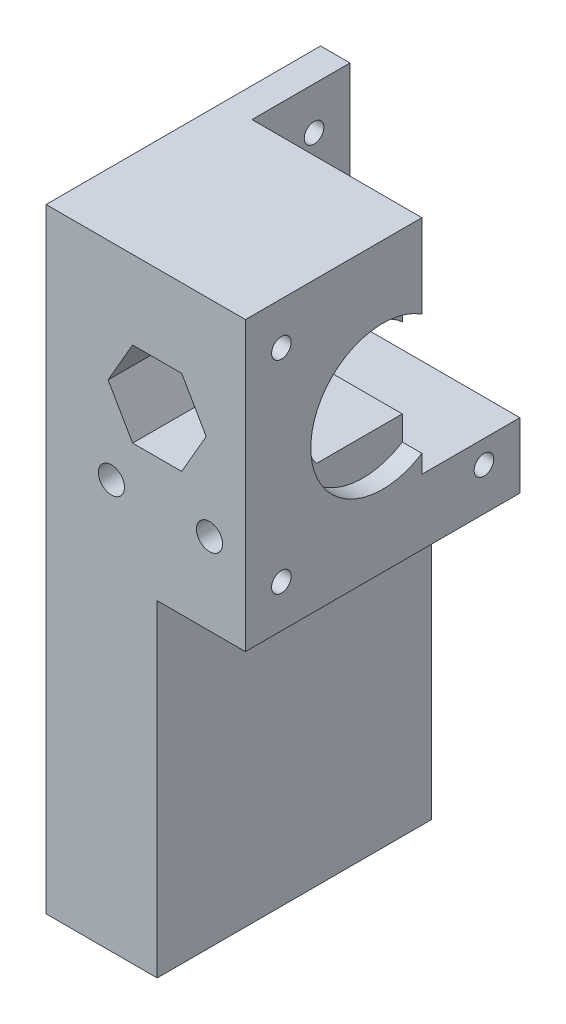
SolidWorks part; units mm, degrees
ref_plane "Front Plane" through (0, 0, 0) normal (0, 0, 1) x (1, 0, 0)
ref_plane "Top Plane" through (0, 0, 0) normal (0, 1, 0) x (1, 0, 0)
ref_plane "Right Plane" through (0, 0, 0) normal (1, 0, 0) x (0, 0, -1)
sketch "Sketch1" plane through (0, 0, 0) normal (0, 0, 1) x (1, 0, 0)
  line L1 (0, 0) -> (30.5, 0)
  line L2 (0, 0) -> (0, 44)
  line L3 (0, 44) -> (30.5, 44)
  line L4 (30.5, 0) -> (30.5, 44)
  line L5 (0, 0) -> (17, 0)
  line L6 (0, 0) -> (0, -50)
  line L7 (0, -50) -> (17, -50)
  line L8 (17, 0) -> (17, -50)
  dimension "D1" = 30.5
  dimension "D2" = 44
  dimension "D3" = 50
  dimension "D4" = 17
extrude "Boss-Extrude1" add sketch "Sketch1" along normal blind 42 contours L1 L4 L3 L2 | L8 L1 L6 L7 region at (15.25, 22, 0) region at (8.5, -25, 0)
sketch "Sketch2" plane through (30.5, 0, 0) normal (1, 0, 0) x (0, 0, -1)
  line L0 (-21, 44) -> (-21, 0) construction
  line L1 (-42, 44) -> (0, 44) construction
  line L2 (-42, 0) -> (0, 0) construction
  line L3 (-42, 22) -> (0, 22) construction
  line L4 (-42, 0) -> (-42, 44) construction
  line L5 (0, 0) -> (0, 44) construction
  circle A0 centre (-21, 22) radius 11
  circle A1 centre (-5.5, 37.5) radius 1.5
  circle A2 centre (-36.5, 37.5) radius 1.5
  circle A3 centre (-36.5, 6.5) radius 1.5
  circle A4 centre (-5.5, 6.5) radius 1.5
  circle A5 centre (-21, 22) radius 9
  point P15 (-21, 22)
  dimension "D1" = 22
  dimension "D2" = 3
  dimension "D3" = 31
  dimension "D4" = 31
  dimension "D5" = 18
extrude "Cut-Extrude1" cut sketch "Sketch2" against normal through all contours A5 | A4 | A3 | A1 | A2
sketch "Sketch4" plane through (30.5, 0, 0) normal (1, 0, 0) x (0, 0, -1)
  line L1 (0, 44) -> (-15, 44)
  line L2 (0, 44) -> (0, 10)
  line L3 (0, 10) -> (-15, 10)
  line L4 (-15, 44) -> (-15, 10)
  dimension "D1" = 15
  dimension "D2" = 34
extrude "Cut-Extrude4" cut sketch "Sketch4" against normal blind 26
sketch "Sketch5" plane through (0, 0, 15) normal (0, 0, -1) x (-1, 0, 0)
  line L1 (-4.5, 10) -> (-27.5, 10)
  line L2 (-4.5, 10) -> (-4.5, 16.5)
  line L3 (-4.5, 16.5) -> (-27.5, 16.5)
  line L4 (-27.5, 10) -> (-27.5, 16.5)
  dimension "D1" = 6.5
  dimension "D2" = 23
extrude "Boss-Extrude2" add sketch "Sketch5" against normal blind 20
sketch "Sketch3" plane through (0, 0, 42) normal (0, 0, 1) x (1, 0, 0)
  line L0 (0, 44) -> (30.5, 44) construction
  line L1 (13.2417, 19) -> (20.7472, 19)
  line L2 (20.7472, 19) -> (24.5, 25.5)
  line L3 (24.5, 25.5) -> (20.7472, 32)
  line L4 (20.7472, 32) -> (13.2417, 32)
  line L5 (13.2417, 32) -> (9.4889, 25.5)
  line L6 (9.4889, 25.5) -> (13.2417, 19)
  line L7 (30.5, 0) -> (30.5, 44) construction
  line L8 (17, 0) -> (30.5, 0) construction
  circle A0 centre (16.9944, 25.5) radius 6.5 construction
  circle A1 centre (25, 12.5) radius 2
  circle A2 centre (10, 12.5) radius 2
  circle A3 centre (25, 12.5) radius 2.5
  circle A4 centre (10, 12.5) radius 2.5
  dimension "D1" = 13
  dimension "D4" = 5.5
  dimension "D5" = 15
  dimension "D6" = 4
  dimension "D7" = 5
  dimension "D8" = 12.5
  dimension "D2" = 12
  dimension "D3" = 6
extrude "Cut-Extrude3" cut sketch "Sketch3" against normal blind 42 contours A2 | A1 | L1 L2 L3 L4 L5 L6 region at (25, 12.5, 42) region at (10, 12.5, 42)
extrude "Cut-Extrude5" cut sketch "Sketch2<3>" against normal blind 3 contours A0 A5 region at (30.5, 22, 31.6889)
sketch "Sketch2<3>" plane through (30.5, 0, 0) normal (1, 0, 0) x (0, 0, -1) same geometry as "Sketch2"
